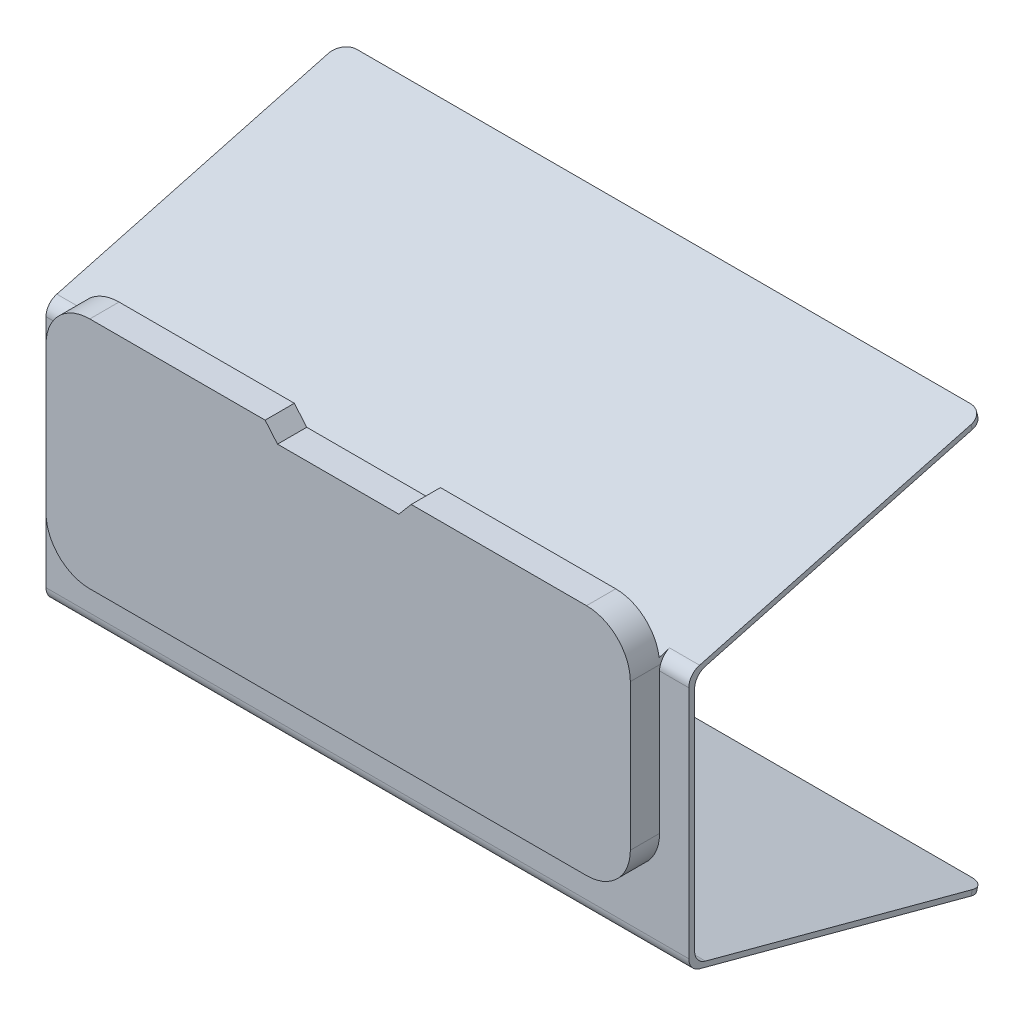
SolidWorks part; units mm, degrees
ref_plane "Front Plane" through (0, 0, 0) normal (0, 0, 1) x (1, 0, 0)
ref_plane "Top Plane" through (0, 0, 0) normal (0, 1, 0) x (1, 0, 0)
ref_plane "Right Plane" through (0, 0, 0) normal (1, 0, 0) x (0, 0, -1)
sketch "Sketch1" plane through (0, 0, 0) normal (0, 0, 1) x (1, 0, 0)
  line L0 (0, 40) -> (0, -40) construction
  line L1 (85, 40) -> (25, 40)
  line L2 (100, 25) -> (100, -25)
  line L3 (85, -40) -> (-85, -40)
  line L4 (-100, 25) -> (-100, -25)
  line L5 (100, 40) -> (-100, -40) construction
  line L6 (100, -40) -> (-100, 40) construction
  line L8 (-25, 40) -> (-85, 40)
  line L9 (-25, 40) -> (-20.7572, 35)
  line L10 (-20.7572, 35) -> (20.7572, 35)
  line L11 (25, 40) -> (20.7572, 35)
  arc A0 (-85, -40) -> (-100, -25) centre (-85, -25) cw
  arc A1 (100, -25) -> (85, -40) centre (85, -25) cw
  arc A2 (85, 40) -> (100, 25) centre (85, 25) cw
  arc A3 (-85, 40) -> (-100, 25) centre (-85, 25) ccw
  point P0 (0, 0)
  point P23 (0, 40)
  point P26 (0, 35)
  dimension "D3" = 15
  dimension "D1" = 200
  dimension "D2" = 80
  dimension "D4" = 50
  dimension "D5" = 75
  dimension "D6" = 20.7572
extrude "Boss-Extrude1" add sketch "Sketch1" along normal blind 10
sketch "Sketch2" plane through (0, 0, 0) normal (0, 0, -1) x (-1, 0, 0)
  line L0 (0, 35) -> (0, -40) construction
  line L1 (-20.7572, 35) -> (20.7572, 35) construction
  line L2 (85, -40) -> (-85, -40) construction
  line L3 (-110, 27) -> (110, 27)
  line L4 (-110, 27) -> (-110, -61)
  line L5 (-110, -61) -> (110, -61)
  line L6 (110, -61) -> (110, 27)
  point P9 (0, 27)
  dimension "D1" = 220
  dimension "D2" = 8
  dimension "D3" = 88
extrude "Boss-Extrude2" add sketch "Sketch2" along normal blind 2
sketch "Sketch3" plane through (110, 0, 0) normal (1, 0, 0) x (0, 0, -1)
  line L0 (2, -17) -> (97.1002, -17) construction
  line L1 (2, 27) -> (2, -61) construction
  line L2 (0, 27) -> (101.4222, 54.176)
  line L10 (0, 27) -> (2, 25.7132)
  line L11 (2, 25.7132) -> (101.8779, 52.4754)
  line L12 (101.4222, 54.176) -> (101.8779, 52.4754)
  line L13 (101.4222, -88.176) -> (101.8779, -86.4754)
  line L14 (2, -59.7132) -> (101.8779, -86.4754)
  line L15 (0, -61) -> (2, -59.7132)
  line L16 (0, -61) -> (101.4222, -88.176)
  dimension "D1" = 105
  dimension "D2" = 105
  dimension "D3" = 103.4012
  dimension "D4" = 105
extrude "Boss-Extrude3" add sketch "Sketch3" against normal up to surface (220 mm away) up to face at (-110, -17, -1)
fillet "Fillet2" radius 5 2 edges at (0, -59.7132, -2) (0, 25.7132, -2)
fillet "Fillet3" radius 5 3 edges at (0, -61, 0) (-104.933, 27, 0) (104.933, 27, 0)
fillet "Fillet4" radius 5 4 edges at (110, 53.3257, -101.6501) (-110, 53.3257, -101.6501) (-110, -87.3257, -101.6501) (110, -87.3257, -101.6501)
